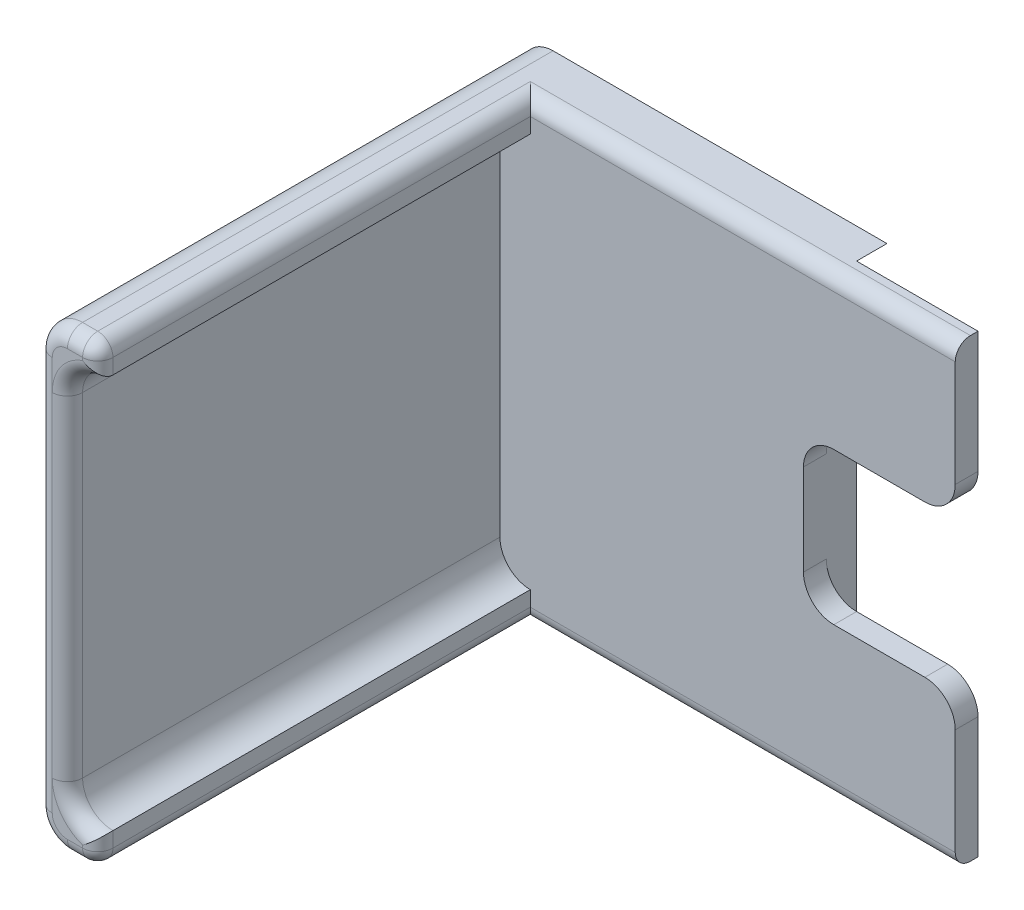
SolidWorks part; units mm, degrees
ref_plane "Front Plane" through (0, 0, 0) normal (0, 0, 1) x (1, 0, 0)
ref_plane "Top Plane" through (0, 0, 0) normal (0, 1, 0) x (1, 0, 0)
ref_plane "Right Plane" through (0, 0, 0) normal (1, 0, 0) x (0, 0, -1)
sketch "Sketch1" plane through (0, 0, 0) normal (0, 0, 1) x (1, 0, 0)
  line L0 (-40, 65) -> (-40, 75)
  line L5 (-60, -65) -> (-60, 65)
  line L6 (-50, -55) -> (-50, 55)
  line L7 (50, 65) -> (50, -65)
  line L9 (-50, -75) -> (60, -75)
  line L10 (50, 0) -> (33.0373, 0) construction
  line L11 (33.0373, 0) -> (33.0373, 45.6927) construction
  line L12 (33.0373, 45.6927) -> (50, 45.6927) construction
  line L13 (60, 75) -> (100, 75)
  line L14 (100, 75) -> (100, 25)
  line L15 (100, 25) -> (50, 25)
  line L16 (60, -75) -> (100, -75)
  line L17 (100, -75) -> (100, -25)
  line L18 (100, -25) -> (50, -25)
  line L19 (50, -65) -> (60, -65)
  line L21 (-40, -65) -> (-40, -75)
  line L22 (-50, 75) -> (60, 75)
  arc A2 (50, -65) -> (60, -75) centre (60, -65) ccw
  arc A3 (50, 65) -> (60, 75) centre (60, 65) cw
  arc A5 (-60, 65) -> (-50, 75) centre (-50, 65) cw
  arc A7 (-50, 55) -> (-40, 65) centre (-40, 55) cw
  arc A8 (-50, -55) -> (-40, -65) centre (-40, -55) ccw
  arc A9 (-50, -75) -> (-60, -65) centre (-50, -65) cw
  point P0 (0, 0)
extrude "Boss-Extrude1" add sketch "Sketch1" along normal blind 7.5 contours L9 A2 L7 A3 | A3 L7 L15 L14 L13 | A2 L16 L17 L18 L7 region at (0.8981, 0, 0) region at (75.1971, 49.8029, 0) region at (75.1971, -49.8029, 0)
extrude "Boss-Extrude2" add sketch "Sketch1<5>" along normal blind 150 contours L9 region at (-53.5711, 0, 0)
sketch "Sketch1<5>" plane through (0, 0, 0) normal (0, 0, 1) x (1, 0, 0) same geometry as "Sketch1"
extrude "Boss-Extrude3" add sketch "Sketch1<6>" against normal blind 10 contours L9 A2 L7 A3 | L9 region at (-53.5711, 0, 0) region at (0.8981, 0, 0)
sketch "Sketch1<6>" plane through (0, 0, 0) normal (0, 0, 1) x (1, 0, 0) same geometry as "Sketch1"
fillet "Fillet1" radius 5 14 edges at (30, 75, 7.5) (30, -75, 7.5) (-45, -75, 150) (-60, 0, 150) (-57.0711, 72.0711, 150) (-45, 75, 150) (-40, 70, 150) (-47.0711, 62.0711, 150) (-50, 0, 150) (-47.0711, -62.0711, 150) (-40, -70, 150) (-57.0711, -72.0711, 150) (-40, 75, 78.75) (-40, -75, 78.75)
fillet "Fillet2" radius 10 2 edges at (100, -25, 3.75) (100, 25, 3.75)
fillet "Fillet3" radius 10 2 edges at (50, -25, 3.75) (50, 25, 3.75)
